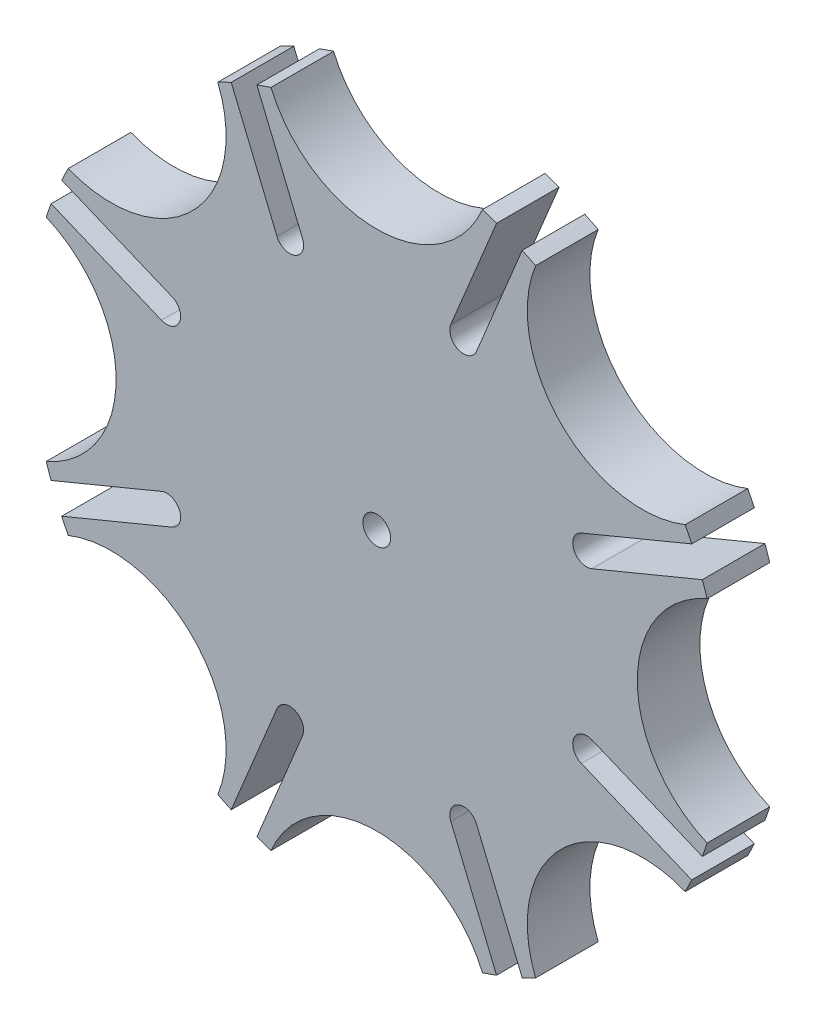
SolidWorks part; units mm, degrees
ref_plane "Front Plane" through (0, 0, 0) normal (0, 0, 1) x (1, 0, 0)
ref_plane "Top Plane" through (0, 0, 0) normal (0, 1, 0) x (1, 0, 0)
ref_plane "Right Plane" through (0, 0, 0) normal (1, 0, 0) x (0, 0, -1)
sketch "Croquis1" plane through (0, 0, 0) normal (0, 0, 1) x (1, 0, 0)
  line L0 (0, 0) -> (-15.1187, 6.2624) construction
  line L1 (0, 0) -> (-18, 0) construction
  line L2 (0, 0) -> (33.8007, 14.0007) construction
  line L3 (0, 0) -> (-10.0606, 4.1672)
  line L4 (-10.0606, 4.1672) -> (-15.364, 6.364) construction
  line L5 (-10.3151, 3.5527) -> (-15.6185, 5.7494)
  line L6 (-9.806, 4.7818) -> (-15.1094, 6.9785)
  line L7 (-18, 0) -> (-15.364, 6.364) construction
  line L8 (-4.1672, 10.0606) -> (-6.364, 15.364) construction
  line L9 (-4.7818, 9.806) -> (-6.9785, 15.1094)
  line L10 (-3.5527, 10.3151) -> (-5.7494, 15.6185)
  line L11 (4.1672, 10.0606) -> (6.364, 15.364) construction
  line L12 (3.5527, 10.3151) -> (5.7494, 15.6185)
  line L13 (4.7818, 9.806) -> (6.9785, 15.1094)
  line L14 (10.0606, 4.1672) -> (15.364, 6.364) construction
  line L45 (-16.2663, 6.7899) -> (-19.2031, 0.5679)
  line L46 (-16.7477, -0.4492) -> (-14.4248, 6.0271)
  line L60 (9.806, 4.7818) -> (15.1094, 6.9785)
  line L75 (10.3151, 3.5527) -> (15.6185, 5.7494)
  line L82 (10.0606, -4.1672) -> (15.364, -6.364) construction
  line L85 (10.3151, -3.5527) -> (15.6185, -5.7494)
  line L88 (9.806, -4.7818) -> (15.1094, -6.9785)
  line L91 (4.1672, -10.0606) -> (6.364, -15.364) construction
  line L92 (4.7818, -9.806) -> (6.9785, -15.1094)
  line L93 (3.5527, -10.3151) -> (5.7494, -15.6185)
  line L94 (-4.1672, -10.0606) -> (-6.364, -15.364) construction
  line L95 (-3.5527, -10.3151) -> (-5.7494, -15.6185)
  line L96 (-4.7818, -9.806) -> (-6.9785, -15.1094)
  line L97 (-10.0606, -4.1672) -> (-15.364, -6.364) construction
  line L98 (-9.806, -4.7818) -> (-15.1094, -6.9785)
  line L99 (-10.3151, -3.5527) -> (-15.6185, -5.7494)
  circle A0 centre (0, 0) radius 16.6298
  circle A7 centre (-18, 0) radius 5.5106
  arc A8 (-10.3151, 3.5527) -> (-9.806, 4.7818) centre (-10.0606, 4.1672) ccw
  arc A9 (-15.1094, 6.9785) -> (-15.6185, 5.7494) centre (-15.364, 6.364) ccw
  circle A10 centre (-12.7279, 12.7279) radius 5.5106
  arc A11 (-4.7818, 9.806) -> (-3.5527, 10.3151) centre (-4.1672, 10.0606) ccw
  arc A12 (-5.7494, 15.6185) -> (-6.9785, 15.1094) centre (-6.364, 15.364) ccw
  circle A13 centre (0, 18) radius 5.5106
  arc A14 (3.5527, 10.3151) -> (4.7818, 9.806) centre (4.1672, 10.0606) ccw
  arc A15 (6.9785, 15.1094) -> (5.7494, 15.6185) centre (6.364, 15.364) ccw
  circle A52 centre (-18, 0) radius 1.3304
  circle A53 centre (-15.364, 6.364) radius 0.9978
  circle A54 centre (0, 0) radius 0.6652
  arc A55 (-12.4894, 0) -> (-22.5301, 3.1377) centre (-12.4894, 17.6341) cw
  circle A56 centre (-18, 0) radius 0.6652
  circle A57 centre (-15.364, 6.364) radius 0.6652
  circle A115 centre (12.7279, 12.7279) radius 5.5106
  arc A116 (9.806, 4.7818) -> (10.3151, 3.5527) centre (10.0606, 4.1672) ccw
  arc A117 (15.6185, 5.7494) -> (15.1094, 6.9785) centre (15.364, 6.364) ccw
  circle A118 centre (18, 0) radius 5.5106
  arc A119 (10.3151, -3.5527) -> (9.806, -4.7818) centre (10.0606, -4.1672) ccw
  arc A120 (15.1094, -6.9785) -> (15.6185, -5.7494) centre (15.364, -6.364) ccw
  circle A121 centre (12.7279, -12.7279) radius 5.5106
  arc A122 (4.7818, -9.806) -> (3.5527, -10.3151) centre (4.1672, -10.0606) ccw
  arc A123 (5.7494, -15.6185) -> (6.9785, -15.1094) centre (6.364, -15.364) ccw
  circle A124 centre (0, -18) radius 5.5106
  arc A125 (-3.5527, -10.3151) -> (-4.7818, -9.806) centre (-4.1672, -10.0606) ccw
  arc A126 (-6.9785, -15.1094) -> (-5.7494, -15.6185) centre (-6.364, -15.364) ccw
  circle A127 centre (-12.7279, -12.7279) radius 5.5106
  arc A128 (-9.806, -4.7818) -> (-10.3151, -3.5527) centre (-10.0606, -4.1672) ccw
  arc A129 (-15.6185, -5.7494) -> (-15.1094, -6.9785) centre (-15.364, -6.364) ccw
  point P4 (-12.7123, 5.2656)
  point P14 (12.7123, 5.2656)
  point P15 (0, 0)
  point P18 (-15.364, 6.364)
  point P20 (-5.2656, 12.7123)
  point P29 (5.2656, 12.7123)
  point P44 (12.7123, -5.2656)
  point P47 (0, 0)
  point P55 (5.2656, -12.7123)
  point P64 (-5.2656, -12.7123)
  point P73 (-12.7123, -5.2656)
  dimension "D4" = 11.0213
  dimension "D8" = 0.6652
  dimension "D3" = 2.6608
  dimension "D9" = 1.3304
  dimension "D11" = 1.9956
  dimension "D12" = 17.6341
  dimension "D13" = 1.3304
  dimension "D1" = 18
  dimension "D2" = 22.5
  dimension "D5" = 45
  dimension "D6" = 36.5856
  dimension "D7" = 10.8895
  dimension "D10" = 8
extrude "Saliente-Extruir1" add sketch "Croquis1" against normal blind 3 contours A0 L13 A14 L12 A13 L10 A11 L9 A10 L6 A8 L5 A7 | A53 A0 A7 L46 L5 | A0 A53 L5 | L6 A53 A0 region at (-9.0321, 4.5932, 0) region at (-15.2113, 5.1032, 0) region at (-14.7832, 6.9872, 0) region at (-15.394, 5.5126, 0)
sketch "Croquis4" [suppressed] plane through (0, 0, 0) normal (0, 0, 1) x (1, 0, 0)
  circle A0 centre (-18, 0) radius 4.9251 construction
  arc A1 (-22.0487, 2.8043) -> (-13.0749, 0) centre (-13.0749, 15.7603) ccw construction
  arc A2 (-22.0487, 2.8043) -> (-13.0749, 0) centre (-18, 0) ccw
  arc A3 (-22.0487, 2.8043) -> (-13.0749, 0) centre (-13.0749, 15.7603) ccw
  circle A4 centre (-18, 0) radius 0.6766 construction
  circle A5 centre (-18, 0) radius 0.6766
  circle A7 centre (-15.8944, 5.7851) radius 0.6766 construction
  circle A9 centre (-15.8944, 5.7851) radius 0.6766
extrude "Saliente-Extruir4" [suppressed] add sketch "Croquis4" against normal blind 3
sketch "Croquis6" [suppressed] plane through (0, 0, 0) normal (0, 0, 1) x (1, 0, 0)
  line L0 (-16.7049, -0.3922) -> (-14.9231, 5.4909) construction
  line L1 (-16.8275, 6.1841) -> (-19.2442, 0.532) construction
  line L2 (-16.7049, -0.3922) -> (-14.9231, 5.4909)
  line L3 (-16.8275, 6.1841) -> (-19.2442, 0.532)
  circle A0 centre (-15.8944, 5.7851) radius 1.0149 construction
  circle A1 centre (-18, 0) radius 1.3532 construction
  arc A2 (-14.9231, 5.4909) -> (-16.8275, 6.1841) centre (-15.8944, 5.7851) ccw
  arc A3 (-19.2442, 0.532) -> (-16.7049, -0.3922) centre (-18, 0) ccw
  circle A6 centre (-18, 0) radius 0.6766 construction
  circle A7 centre (-18, 0) radius 0.6766
extrude "Saliente-Extruir5" [suppressed] add sketch "Croquis6" along normal blind 3
sketch "Croquis7" [suppressed] plane through (0, 0, 0) normal (0, 0, 1) x (1, 0, 0)
  circle A0 centre (0, 0) radius 0.6766 construction
  circle A1 centre (-18, 0) radius 0.6766 construction
  circle A2 centre (0, 0) radius 0.6766
  circle A3 centre (-18, 0) radius 0.6766
extrude "Saliente-Extruir6" [suppressed] add sketch "Croquis7" against normal blind 18 and the other way blind 3
sketch "Croquis8" [suppressed] plane through (0, 0, -18) normal (0, 0, -1) x (-1, 0, 0)
  line L0 (0, -4.9251) -> (18, -4.9251)
  line L1 (0, 4.9251) -> (18, 4.9251)
  circle A0 centre (18, 0) radius 4.9251 construction
  arc A1 (18, -4.9251) -> (18, 4.9251) centre (18, 0) ccw
  arc A2 (0, 4.9251) -> (0, -4.9251) centre (0, 0) ccw
extrude "Saliente-Extruir7" [suppressed] add sketch "Croquis8" along normal blind 6
equation "\"S\"= ( \"d\" - \"a\" ) * 0.98"
equation "\"R\"= \"d\" * cos ( \"Bo\" / 2 ) * 2"
equation "\"n\"= 8"
equation "\"Bo\"= 360 / \"n\""
equation "\"din\"= \"d\" / 10"
equation "\"d\"=18"
equation "\"D4@Croquis1\"= \"D2\""
equation "\"D1@Croquis1\"=\"d\""
equation "\"D2@Croquis1\"=\"Bo\"/2"
equation "\"D5@Croquis1\"=\"Bo\""
equation "\"D6@Croquis1\"=\"R\"*1.1"
equation "\"D7@Croquis1\"=\"S\""
equation "\"R1\"= \"R\" / 50"
equation "\"D8@Croquis1\"=\"R1\""
equation "\"a\"= \"d\" * sin ( \"Bo\" / 2 )"
equation "\"ancho\"= 3"
equation "\"D1@Saliente-Extruir1\"=\"ancho\""
equation "\"D10@Croquis1\"=\"n\""
equation "\"D2\"= 1.6 * \"a\""
equation "\"D3@Croquis1\"=4*\"R1\""
equation "\"D9@Croquis1\"=2*\"R1\""
equation "\"D11@Croquis1\"=3*\"R1\""
equation "\"D12@Croquis1\"=\"D2\"/2*3.2"
equation "\"D13@Croquis1\"=2*\"R1\""
equation "\"D1@Saliente-Extruir7\"=\"ancho\"*2"
equation "\"D1@Saliente-Extruir6\"=\"ancho\"*6"
equation "\"D2@Saliente-Extruir6\"=\"ancho\""
equation "\"D1@Saliente-Extruir5\"=\"ancho\""
equation "\"D1@Saliente-Extruir4\"=\"ancho\""
